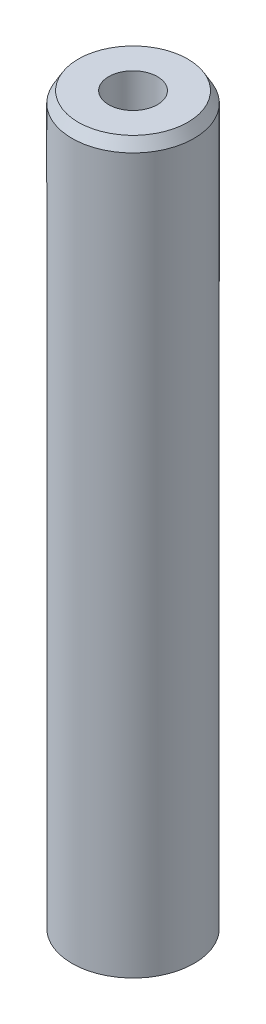
SolidWorks part; units mm, degrees
ref_plane "Front Plane" through (0, 0, 0) normal (0, 0, 1) x (1, 0, 0)
ref_plane "Top Plane" through (0, 0, 0) normal (0, 1, 0) x (1, 0, 0)
ref_plane "Right Plane" through (0, 0, 0) normal (1, 0, 0) x (0, 0, -1)
sketch "Sketch1" plane through (0, 0, 0) normal (0, 1, 0) x (1, 0, 0)
  circle A0 centre (0, 0) radius 30
  dimension "SHAFT_OD" = 60
extrude "Boss-Extrude1" add sketch "Sketch1" along normal blind 359.631
sketch "Sketch2" plane through (0, 0, 0) normal (0, 1, 0) x (1, 0, 0)
  circle A0 centre (0, 0) radius 11.9721
  dimension "BORE_D" = 23.9443
extrude "Cut-Extrude1" cut sketch "Sketch2" along normal through all
chamfer "Chamfer1" distance 5.3312 angle 30 2 edges at (0, 359.631, 30) (0, 0, 30) first distance on face at (0, 359.631, 30) first distance on face at (0, 0, 11.9721)
